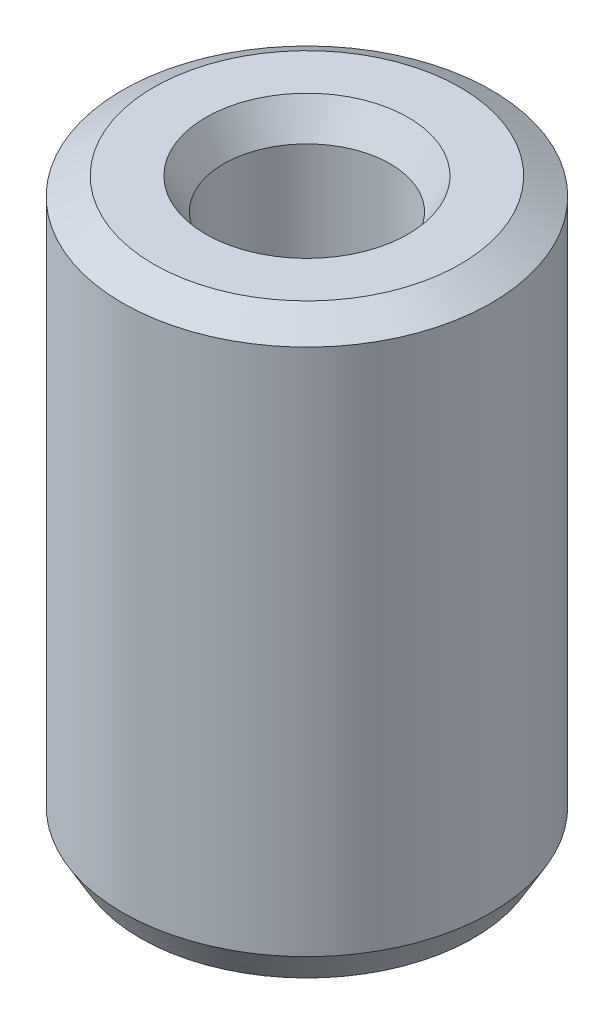
SolidWorks part; units mm, degrees
ref_plane "Front Plane" through (0, 0, 0) normal (0, 0, 1) x (1, 0, 0)
ref_plane "Top Plane" through (0, 0, 0) normal (0, 1, 0) x (1, 0, 0)
ref_plane "Right Plane" through (0, 0, 0) normal (1, 0, 0) x (0, 0, -1)
sketch "Sketch1" plane through (0, 0, 0) normal (0, 1, 0) x (1, 0, 0)
  circle A0 centre (0, 0) radius 20
  dimension "SLEEVE_OD" = 40
extrude "Boss-Extrude1" add sketch "Sketch1" along normal blind 62.5793
sketch "Sketch2" plane through (0, 0, 0) normal (0, 1, 0) x (1, 0, 0)
  circle A0 centre (0, 0) radius 9.023
  dimension "BORE_D" = 18.046
extrude "Cut-Extrude1" cut sketch "Sketch2" along normal through all
chamfer "Chamfer1" distance 1.9511 angle 60 4 edges at (0, 62.5793, 9.023) (0, 0, 9.023) (0, 0, 20) (0, 62.5793, 20) first distance on face at (0, 62.5793, 9.023) first distance on face at (0, 0, 9.023) first distance on face at (0, 62.5793, 20)
